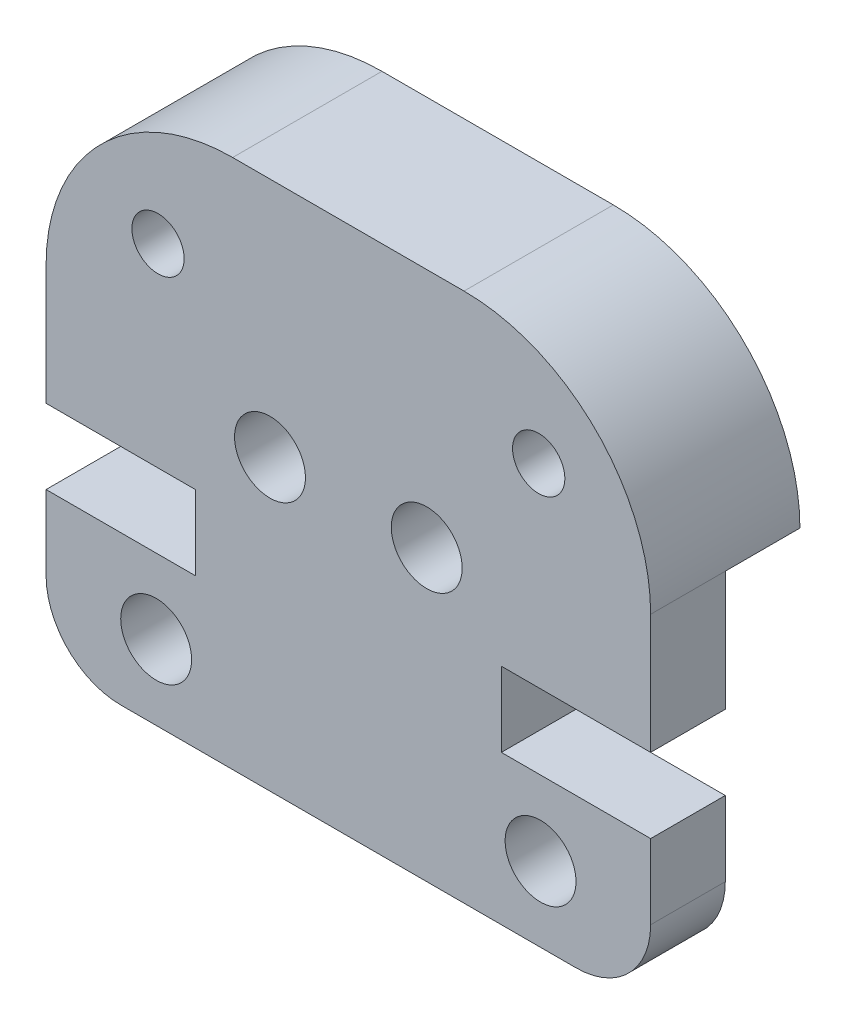
SolidWorks part; units mm, degrees
ref_plane "Front Plane" through (0, 0, 0) normal (0, 0, 1) x (1, 0, 0)
ref_plane "Top Plane" through (0, 0, 0) normal (0, 1, 0) x (1, 0, 0)
ref_plane "Right Plane" through (0, 0, 0) normal (1, 0, 0) x (0, 0, -1)
sketch "Sketch1" plane through (0, 0, 0) normal (0, 0, 1) x (1, 0, 0)
  line L0 (8.1, 14.205) -> (8.1, 0) construction
  line L1 (12.2, 4) -> (16.2, 4)
  line L2 (12.2, 6) -> (12.2, 4)
  line L3 (16.2, 6) -> (12.2, 6)
  line L4 (16.2, 2) -> (16.2, 4)
  line L5 (16.2, 9.205) -> (16.2, 6)
  line L14 (0, 9.205) -> (0, 6)
  line L15 (5, 14.205) -> (11.2, 14.205)
  line L16 (2, 0) -> (14.2, 0)
  line L18 (0, 2) -> (0, 4)
  line L19 (0, 6) -> (4, 6)
  line L21 (4, 6) -> (4, 4)
  line L22 (4, 4) -> (0, 4)
  circle A0 centre (13.25, 2) radius 0.95
  arc A1 (16.2, 2) -> (14.2, 0) centre (14.2, 2) cw
  circle A2 centre (13.2, 11.205) radius 0.7
  arc A3 (11.2, 14.205) -> (16.2, 9.205) centre (11.2, 9.205) cw
  circle A4 centre (10.2, 7.75) radius 0.95
  circle A11 centre (6, 7.75) radius 0.95
  arc A13 (5, 14.205) -> (0, 9.205) centre (5, 9.205) ccw
  circle A15 centre (3, 11.205) radius 0.7
  arc A17 (0, 2) -> (2, 0) centre (2, 2) ccw
  circle A19 centre (2.95, 2) radius 0.95
  dimension "D1" = 1.4
  dimension "D2" = 1.9
  dimension "D3" = 5
  dimension "D4" = 2
  dimension "D5" = 3
  dimension "D6" = 6
  dimension "D7" = 8.1
  dimension "D8" = 7.75
  dimension "D10" = 14.205
  dimension "D9" = 3
extrude "Boss-Extrude1" add sketch "Sketch1" along normal blind 4
sketch "Sketch2" plane through (0, 0, 0) normal (0, 0, -1) x (-1, 0, 0)
  line L0 (0, 0) -> (0, 9.205)
  line L1 (0, 9.205) -> (-16.2, 9.205)
  line L2 (-16.2, 9.205) -> (-16.2, 0)
  line L3 (-16.2, 0) -> (0, 0)
extrude "Cut-Extrude1" cut sketch "Sketch2" against normal blind 2
equation "\"D7@Sketch1\"= \"fingerWidth@parametersSketch@prostheticParameters.SLDPRT\" / 2 'DIP width"
equation "\"D10@Sketch1\"= \"HL@parametersSketch@prostheticParameters.SLDPRT\" * 0.093 - 3 'DIP length - Sil. Sht DIP"
equation "\"D1@Sketch1\"= 1 + \"tol1@parametersSketch@prostheticParameters.SLDPRT\""
equation "\"D2@Sketch1\"= 1.5 + \"tol1@parametersSketch@prostheticParameters.SLDPRT\""
